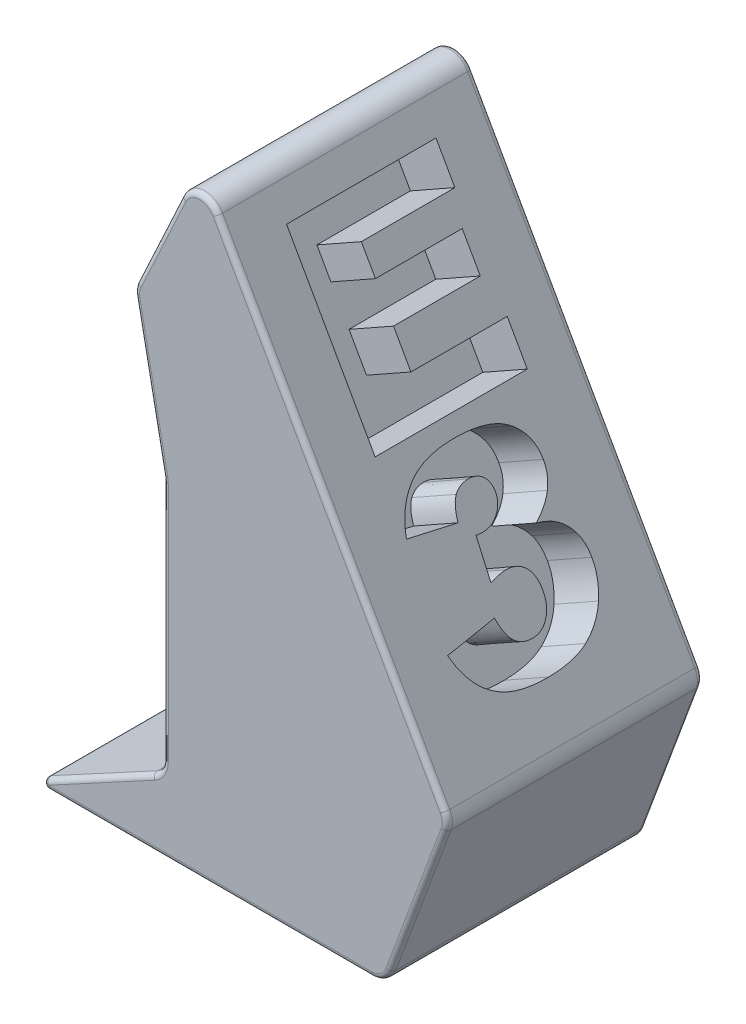
SolidWorks part; units mm, degrees
ref_plane "Alzado" through (0, 0, 0) normal (0, 0, 1) x (1, 0, 0)
ref_plane "Planta" through (0, 0, 0) normal (0, 1, 0) x (1, 0, 0)
ref_plane "Vista lateral" through (0, 0, 0) normal (1, 0, 0) x (0, 0, -1)
sketch "Sketch5" plane through (0, 0, 0) normal (0, 0, 1) x (1, 0, 0)
  line L0 (0, 0) -> (672.1713, 0)
  line L3 (740.3315, 484.8927) -> (370.4823, 1141.2206)
  line L5 (208.5032, 924.2833) -> (263.1478, 646.5009)
  line L6 (263.9, 638.7802) -> (263.9, 166.523)
  line L7 (242.9237, 131.3363) -> (0, 0)
  line L8 (299.3441, 1138.4064) -> (211.4608, 948.8271)
  line L9 (740.3315, 484.8927) -> (815.3488, 351.7684)
  line L10 (818.0053, 318.2236) -> (709.6757, 26.0924)
  arc A1 (815.3488, 351.7684) -> (818.0053, 318.2236) centre (780.5009, 332.1312) cw
  arc A2 (672.1713, 0) -> (709.6757, 26.0924) centre (672.1713, 40) ccw
  arc A3 (263.9, 166.523) -> (242.9237, 131.3363) centre (223.9, 166.523) cw
  arc A4 (263.1478, 646.5009) -> (263.9, 638.7802) centre (223.9, 638.7802) cw
  arc A5 (211.4608, 948.8271) -> (208.5032, 924.2833) centre (247.751, 932.0041) ccw
  arc A6 (370.4823, 1141.2206) -> (299.3441, 1138.4064) centre (335.6343, 1121.5833) ccw
  point P19 (577.6335, 773.6137)
  point P24 (700, 0)
  point P27 (263.9, 142.6772)
  point P30 (263.9, 642.6772)
  point P33 (205.9946, 937.0357)
  point P36 (332.1678, 1209.2127)
  dimension "D1" = 300
  dimension "D2" = 500
  dimension "D3" = 300
  dimension "D4" = 500
  dimension "D7" = 700
  dimension "D8" = 300
extrude "Boss-Extrude4" add sketch "Sketch5" along normal blind 250 and the other way blind 250
fillet "Fillet1" radius 10 13 edges at (258.258, 146.0406, 250) (263.9, 402.6516, 250) (263.7115, 642.6588, 250) (235.8255, 785.3921, 250) (208.0383, 936.7895, 250) (255.4024, 1043.6168, 250) (334.0532, 1161.552, 250) (592.9155, 746.4945, 250) (820.3761, 335.2889, 250) (763.8405, 172.158, 250) (695.0153, 7.1648, 250) (336.0857, 0, 250) (121.4618, 65.6682, 250)
fillet "Fillet2" radius 10 13 edges at (336.0857, 0, -250) (695.0153, 7.1648, -250) (763.8405, 172.158, -250) (820.3761, 335.2889, -250) (592.9155, 746.4945, -250) (334.0532, 1161.552, -250) (255.4024, 1043.6168, -250) (208.0383, 936.7895, -250) (235.8255, 785.3921, -250) (263.7115, 642.6588, -250) (263.9, 402.6516, -250) (258.258, 146.0406, -250) (121.4618, 65.6682, -250)
fillet "Fillet3" radius 10 3 edges at (11.576, 2.9289, -247.0711) (11.576, 2.9289, 247.0711) (0, 0, 0)
sketch "Sketch11" plane through (769.2894, 433.5046, 0) normal (0.8712, 0.4909, 0) x (0, 0, -1)
  line L0 (-144.2111, 752.5076) -> (148.552, 752.5076)
  line L1 (148.552, 752.5076) -> (148.552, 677.0259)
  line L2 (148.552, 677.0259) -> (-34.7264, 677.0259)
  line L3 (-34.7264, 677.0259) -> (-34.7264, 620.8366)
  line L4 (-34.7264, 620.8366) -> (135.2884, 620.8366)
  line L5 (135.2884, 620.8366) -> (135.2884, 548.731)
  line L6 (135.2884, 548.731) -> (-34.7264, 548.731)
  line L7 (-34.7264, 548.731) -> (-34.7264, 479.037)
  line L8 (-34.7264, 479.037) -> (153.8574, 479.037)
  line L9 (153.8574, 479.037) -> (153.8574, 398.9733)
  line L10 (153.8574, 398.9733) -> (-144.2111, 398.9733)
  line L11 (-144.2111, 398.9733) -> (-144.2111, 752.5076)
  line L12 (-51.3662, 257.3132) -> (-144.2111, 273.9529)
  line L13 (-149.5166, 99.3562) -> (-51.3662, 112.3786)
  line L14 (-35.2087, 158.6805) -> (-30.1445, 228.8568)
  spline S0 degree 3 poles (-144.2111, 273.9529) (-136.4942, 303.5347) (-121.7033, 326.2034) (-99.8385, 341.9589) knots 0 0 0 0 1 1 1 1
  spline S1 degree 3 poles (-99.8385, 341.9589) (-77.8129, 357.7144) (-46.7038, 365.5921) (-6.5112, 365.5921) knots 0 0 0 0 1 1 1 1
  spline S2 degree 3 poles (-6.5112, 365.5921) (39.6299, 365.5921) (72.9898, 356.9909) (93.5685, 339.7885) knots 0 0 0 0 1 1 1 1
  spline S3 degree 3 poles (93.5685, 339.7885) (114.1471, 322.586) (124.4364, 300.9624) (124.4364, 274.9176) knots 0 0 0 0 1 1 1 1
  spline S4 degree 3 poles (124.4364, 274.9176) (124.4364, 259.6444) (120.2564, 245.8181) (111.8963, 233.4388) knots 0 0 0 0 1 1 1 1
  spline S5 degree 3 poles (111.8963, 233.4388) (103.5362, 221.0594) (90.9157, 210.2074) (74.0348, 200.8828) knots 0 0 0 0 1 1 1 1
  spline S6 degree 3 poles (74.0348, 200.8828) (87.7003, 197.5066) (98.1504, 193.5677) (105.3851, 189.0661) knots 0 0 0 0 1 1 1 1
  spline S7 degree 3 poles (105.3851, 189.0661) (117.1213, 181.8314) (126.2048, 172.2656) (132.6357, 160.3686) knots 0 0 0 0 1 1 1 1
  spline S8 degree 3 poles (132.6357, 160.3686) (139.2273, 148.6323) (142.5231, 134.5649) (142.5231, 118.1663) knots 0 0 0 0 1 1 1 1
  spline S9 degree 3 poles (142.5231, 118.1663) (142.5231, 97.5877) (137.1373, 77.8129) (126.3656, 58.842) knots 0 0 0 0 1 1 1 1
  spline S10 degree 3 poles (126.3656, 58.842) (115.594, 40.0318) (100.0797, 25.4821) (79.8226, 15.1928) knots 0 0 0 0 1 1 1 1
  spline S11 degree 3 poles (79.8226, 15.1928) (59.5655, 5.0643) (32.9579, 0) (0, 0) knots 0 0 0 0 1 1 1 1
  spline S12 degree 3 poles (0, 0) (-32.1541, 0) (-57.5558, 3.7781) (-76.2052, 11.3343) knots 0 0 0 0 1 1 1 1
  spline S13 degree 3 poles (-76.2052, 11.3343) (-94.6938, 18.8905) (-109.967, 29.9033) (-122.0248, 44.3726) knots 0 0 0 0 1 1 1 1
  spline S14 degree 3 poles (-122.0248, 44.3726) (-133.9218, 59.0028) (-143.0858, 77.3306) (-149.5166, 99.3562) knots 0 0 0 0 1 1 1 1
  spline S15 degree 3 poles (-51.3662, 112.3786) (-47.5077, 92.6038) (-41.5592, 78.8579) (-33.5206, 71.141) knots 0 0 0 0 1 1 1 1
  spline S16 degree 3 poles (-33.5206, 71.141) (-25.3213, 63.5847) (-14.9516, 59.8066) (-2.4116, 59.8066) knots 0 0 0 0 1 1 1 1
  spline S17 degree 3 poles (-2.4116, 59.8066) (10.7716, 59.8066) (21.704, 64.6297) (30.3856, 74.276) knots 0 0 0 0 1 1 1 1
  spline S18 degree 3 poles (30.3856, 74.276) (39.228, 83.9222) (43.6492, 96.7838) (43.6492, 112.8609) knots 0 0 0 0 1 1 1 1
  spline S19 degree 3 poles (43.6492, 112.8609) (43.6492, 129.2595) (39.3888, 141.9604) (30.868, 150.9635) knots 0 0 0 0 1 1 1 1
  spline S20 degree 3 poles (30.868, 150.9635) (22.5079, 159.9666) (11.0932, 164.4682) (-3.3762, 164.4682) knots 0 0 0 0 1 1 1 1
  spline S21 degree 3 poles (-3.3762, 164.4682) (-11.0931, 164.4682) (-21.704, 162.539) (-35.2087, 158.6805) knots 0 0 0 0 1 1 1 1
  spline S22 degree 3 poles (-30.1445, 228.8568) (-24.6783, 228.0529) (-20.4178, 227.651) (-17.3632, 227.651) knots 0 0 0 0 1 1 1 1
  spline S23 degree 3 poles (-17.3632, 227.651) (-4.5015, 227.651) (6.1897, 231.7507) (14.7105, 239.95) knots 0 0 0 0 1 1 1 1
  spline S24 degree 3 poles (14.7105, 239.95) (23.3921, 248.1493) (27.7329, 257.8759) (27.7329, 269.1298) knots 0 0 0 0 1 1 1 1
  spline S25 degree 3 poles (27.7329, 269.1298) (27.7329, 279.9015) (24.5175, 288.5027) (18.0867, 294.9335) knots 0 0 0 0 1 1 1 1
  spline S26 degree 3 poles (18.0867, 294.9335) (11.6559, 301.3643) (2.8135, 304.5797) (-8.4405, 304.5797) knots 0 0 0 0 1 1 1 1
  spline S27 degree 3 poles (-8.4405, 304.5797) (-20.0159, 304.5797) (-29.421, 301.0428) (-36.6557, 293.9689) knots 0 0 0 0 1 1 1 1
  spline S28 degree 3 poles (-36.6557, 293.9689) (-43.8903, 287.0557) (-48.7938, 274.8372) (-51.3662, 257.3132) knots 0 0 0 0 1 1 1 1
extrude "Cut-Extrude1" cut sketch "Sketch11" against normal blind 100
